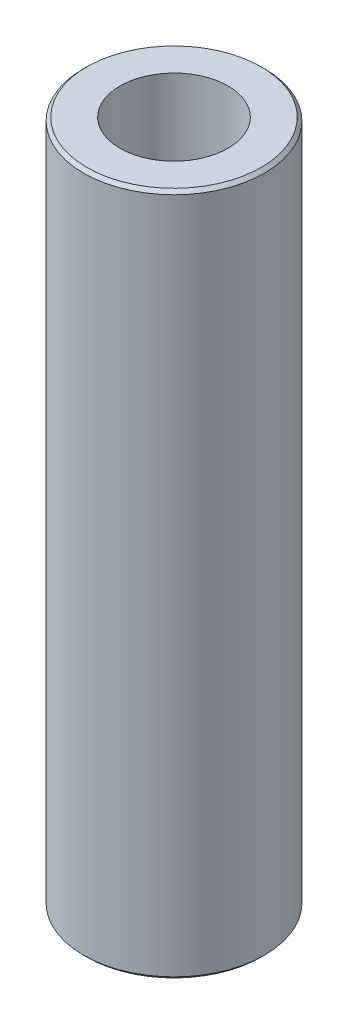
SolidWorks part; units mm, degrees
ref_plane "Front Plane" through (0, 0, 0) normal (0, 0, 1) x (1, 0, 0)
ref_plane "Top Plane" through (0, 0, 0) normal (0, 1, 0) x (1, 0, 0)
ref_plane "Right Plane" through (0, 0, 0) normal (1, 0, 0) x (0, 0, -1)
sketch "Sketch1" plane through (0, 0, 0) normal (0, 1, 0) x (1, 0, 0)
  circle A0 centre (0, 0) radius 10
  dimension "SHAFT_OD" = 20
extrude "Boss-Extrude1" add sketch "Sketch1" along normal blind 75.5907
sketch "Sketch2" plane through (0, 0, 0) normal (0, 1, 0) x (1, 0, 0)
  circle A0 centre (0, 0) radius 5.9725
  dimension "BORE_D" = 11.9451
extrude "Cut-Extrude1" cut sketch "Sketch2" along normal through all
chamfer "Chamfer1" distance 0.3636 angle 45 2 edges at (0, 75.5907, 10) (0, 0, 10)
